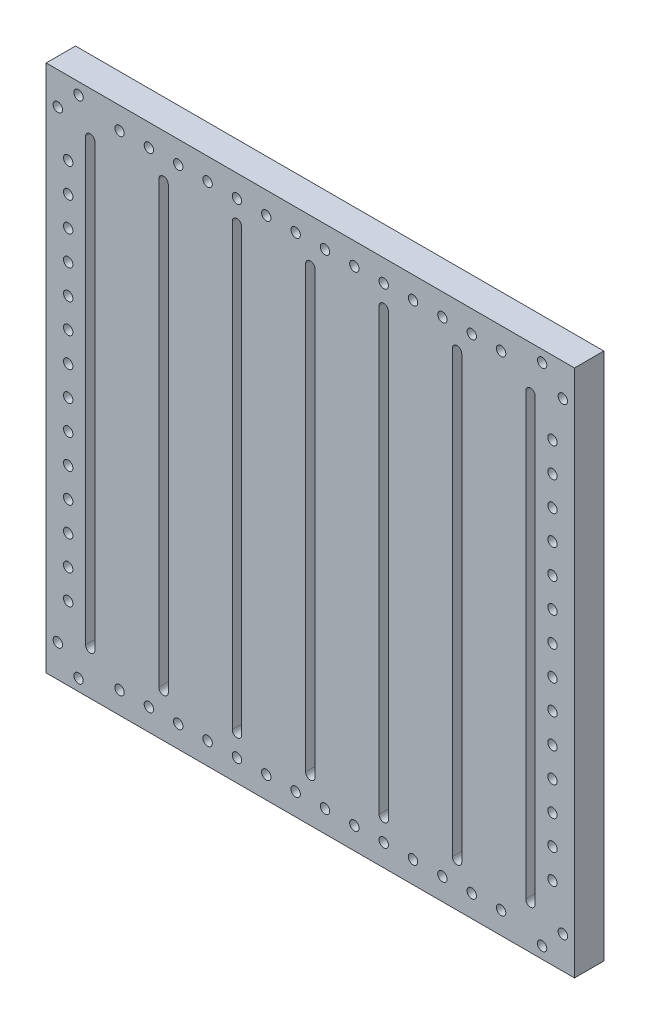
SolidWorks part; units mm, degrees
ref_plane "Front Plane" through (0, 0, 0) normal (0, 0, 1) x (1, 0, 0)
ref_plane "Top Plane" through (0, 0, 0) normal (0, 1, 0) x (1, 0, 0)
ref_plane "Right Plane" through (0, 0, 0) normal (1, 0, 0) x (0, 0, -1)
sketch "Sketch1" plane through (0, 0, 0) normal (0, 0, 1) x (1, 0, 0)
  line L0 (0, 90) -> (0, -90) construction
  line L1 (90, -90) -> (-90, -90)
  line L2 (90, -90) -> (90, 90)
  line L3 (90, 90) -> (-90, 90)
  line L4 (-90, -90) -> (-90, 90)
  line L5 (90, -90) -> (-90, 90) construction
  line L6 (90, 90) -> (-90, -90) construction
  line L7 (-1.6, 75) -> (-1.6, -75)
  line L8 (1.6, 75) -> (1.6, -75)
  line L9 (-1.6, 75) -> (1.6, 75) construction
  line L10 (-1.6, -75) -> (1.6, -75) construction
  line L11 (-1.6, -75) -> (-1.6, -90) construction
  line L12 (1.6, -75) -> (1.6, -90) construction
  line L13 (23.4, 75) -> (23.4, -75)
  line L14 (26.6, 75) -> (26.6, -75)
  line L15 (48.4, 75) -> (48.4, -75)
  line L16 (51.6, 75) -> (51.6, -75)
  line L17 (73.4, 75) -> (73.4, -75)
  line L18 (76.6, 75) -> (76.6, -75)
  line L19 (-26.6, 75) -> (-26.6, -75)
  line L20 (-23.4, 75) -> (-23.4, -75)
  line L21 (-51.6, 75) -> (-51.6, -75)
  line L22 (-48.4, 75) -> (-48.4, -75)
  line L23 (-76.6, 75) -> (-76.6, -75)
  line L24 (-73.4, 75) -> (-73.4, -75)
  line L25 (25, 76.6) -> (25, -76.6) construction
  line L26 (-25, 76.6) -> (-25, -76.6) construction
  line L27 (-90, 82.5) -> (90, 82.5) construction
  line L28 (82.5, 90) -> (82.5, -90) construction
  line L29 (90, -82.5) -> (-90, -82.5) construction
  line L30 (-82.5, 90) -> (-82.5, -90) construction
  line L31 (-86.0355, 78.9645) -> (-78.9645, 86.0355) construction
  line L32 (78.9645, 86.0355) -> (86.0355, 78.9645) construction
  line L33 (86.0355, -78.9645) -> (78.9645, -86.0355) construction
  line L34 (-78.9645, -86.0355) -> (-86.0355, -78.9645) construction
  arc A0 (1.6, 75) -> (-1.6, 75) centre (0, 75) ccw
  arc A1 (-1.6, 75) -> (0, 73.4) centre (0, 75) ccw construction
  arc A2 (0, 73.4) -> (1.6, 75) centre (0, 75) ccw construction
  arc A3 (-1.6, -75) -> (1.6, -75) centre (0, -75) ccw
  arc A4 (0, -73.4) -> (-1.6, -75) centre (0, -75) ccw construction
  arc A5 (1.6, -75) -> (0, -73.4) centre (0, -75) ccw construction
  arc A6 (23.4, -75) -> (26.6, -75) centre (25, -75) ccw
  arc A7 (26.6, 75) -> (23.4, 75) centre (25, 75) ccw
  arc A8 (48.4, -75) -> (51.6, -75) centre (50, -75) ccw
  arc A9 (51.6, 75) -> (48.4, 75) centre (50, 75) ccw
  arc A10 (73.4, -75) -> (76.6, -75) centre (75, -75) ccw
  arc A11 (76.6, 75) -> (73.4, 75) centre (75, 75) ccw
  arc A12 (-26.6, -75) -> (-23.4, -75) centre (-25, -75) ccw
  arc A13 (-23.4, 75) -> (-26.6, 75) centre (-25, 75) ccw
  arc A14 (-51.6, -75) -> (-48.4, -75) centre (-50, -75) ccw
  arc A15 (-48.4, 75) -> (-51.6, 75) centre (-50, 75) ccw
  arc A16 (-76.6, -75) -> (-73.4, -75) centre (-75, -75) ccw
  arc A17 (-73.4, 75) -> (-76.6, 75) centre (-75, 75) ccw
  circle A18 centre (-78.9645, 86.0355) radius 1.6
  circle A19 centre (-86.0355, 78.9645) radius 1.6
  circle A20 centre (78.9645, 86.0355) radius 1.6
  circle A21 centre (86.0355, 78.9645) radius 1.6
  circle A22 centre (86.0355, -78.9645) radius 1.6
  circle A23 centre (78.9645, -86.0355) radius 1.6
  circle A24 centre (-78.9645, -86.0355) radius 1.6
  circle A25 centre (-86.0355, -78.9645) radius 1.6
  circle A26 centre (-5, 82.5) radius 1.6
  circle A27 centre (5, 82.5) radius 1.6
  circle A28 centre (-15, 82.5) radius 1.6
  circle A29 centre (-25, 82.5) radius 1.6
  circle A30 centre (-35, 82.5) radius 1.6
  circle A31 centre (-45, 82.5) radius 1.6
  circle A32 centre (-55, 82.5) radius 1.6
  circle A33 centre (-65, 82.5) radius 1.6
  circle A34 centre (15, 82.5) radius 1.6
  circle A35 centre (25, 82.5) radius 1.6
  circle A36 centre (35, 82.5) radius 1.6
  circle A37 centre (45, 82.5) radius 1.6
  circle A38 centre (55, 82.5) radius 1.6
  circle A39 centre (65, 82.5) radius 1.6
  circle A40 centre (82.5, 65) radius 1.6
  circle A41 centre (82.5, 55) radius 1.6
  circle A42 centre (82.5, 45) radius 1.6
  circle A43 centre (82.5, 35) radius 1.6
  circle A44 centre (82.5, 25) radius 1.6
  circle A45 centre (82.5, 15) radius 1.6
  circle A46 centre (82.5, 5) radius 1.6
  circle A47 centre (82.5, -5) radius 1.6
  circle A48 centre (82.5, -15) radius 1.6
  circle A49 centre (82.5, -25) radius 1.6
  circle A50 centre (82.5, -35) radius 1.6
  circle A51 centre (82.5, -45) radius 1.6
  circle A52 centre (82.5, -55) radius 1.6
  circle A53 centre (82.5, -65) radius 1.6
  circle A54 centre (65, -82.5) radius 1.6
  circle A55 centre (55, -82.5) radius 1.6
  circle A56 centre (45, -82.5) radius 1.6
  circle A57 centre (35, -82.5) radius 1.6
  circle A58 centre (25, -82.5) radius 1.6
  circle A59 centre (15, -82.5) radius 1.6
  circle A60 centre (5, -82.5) radius 1.6
  circle A61 centre (-5, -82.5) radius 1.6
  circle A62 centre (-15, -82.5) radius 1.6
  circle A63 centre (-25, -82.5) radius 1.6
  circle A64 centre (-35, -82.5) radius 1.6
  circle A65 centre (-45, -82.5) radius 1.6
  circle A66 centre (-55, -82.5) radius 1.6
  circle A67 centre (-65, -82.5) radius 1.6
  circle A68 centre (-82.5, -65) radius 1.6
  circle A69 centre (-82.5, -55) radius 1.6
  circle A70 centre (-82.5, -45) radius 1.6
  circle A71 centre (-82.5, -35) radius 1.6
  circle A72 centre (-82.5, -25) radius 1.6
  circle A73 centre (-82.5, -15) radius 1.6
  circle A74 centre (-82.5, -5) radius 1.6
  circle A75 centre (-82.5, 5) radius 1.6
  circle A76 centre (-82.5, 15) radius 1.6
  circle A77 centre (-82.5, 25) radius 1.6
  circle A78 centre (-82.5, 35) radius 1.6
  circle A79 centre (-82.5, 45) radius 1.6
  circle A80 centre (-82.5, 55) radius 1.6
  circle A81 centre (-82.5, 65) radius 1.6
  point P0 (0, 0)
  point P68 (-82.5, 82.5)
  point P71 (-82.5, -82.5)
  point P86 (0, 0)
  point P200 (0, 0)
  dimension "D18" = 3.2
  dimension "D19" = 3.2
  dimension "D21" = 3.2
  dimension "D22" = 3.2
  dimension "D1" = 180
  dimension "D2" = 180
  dimension "D3" = 1.6
  dimension "D4" = 1.6
  dimension "D5" = 15
  dimension "D6" = 15
  dimension "D7" = 4
  dimension "D9" = 25
  dimension "D10" = 25
  dimension "D11" = 7.5
  dimension "D12" = 7.5
  dimension "D13" = 7.5
  dimension "D14" = 7.5
  dimension "D15" = 10
  dimension "D16" = 0
  dimension "D17" = 82.5
  dimension "D23" = 10
  dimension "D24" = 5
  dimension "D26" = 10
  dimension "D28" = 10
  dimension "D30" = 17.5
  dimension "D31" = 5
  dimension "D8" = 4
  dimension "D25" = 7
  dimension "D27" = 7
  dimension "D20" = 4
  dimension "D29" = 4
extrude "Boss-Extrude1" add sketch "Sketch1" along normal blind 10
